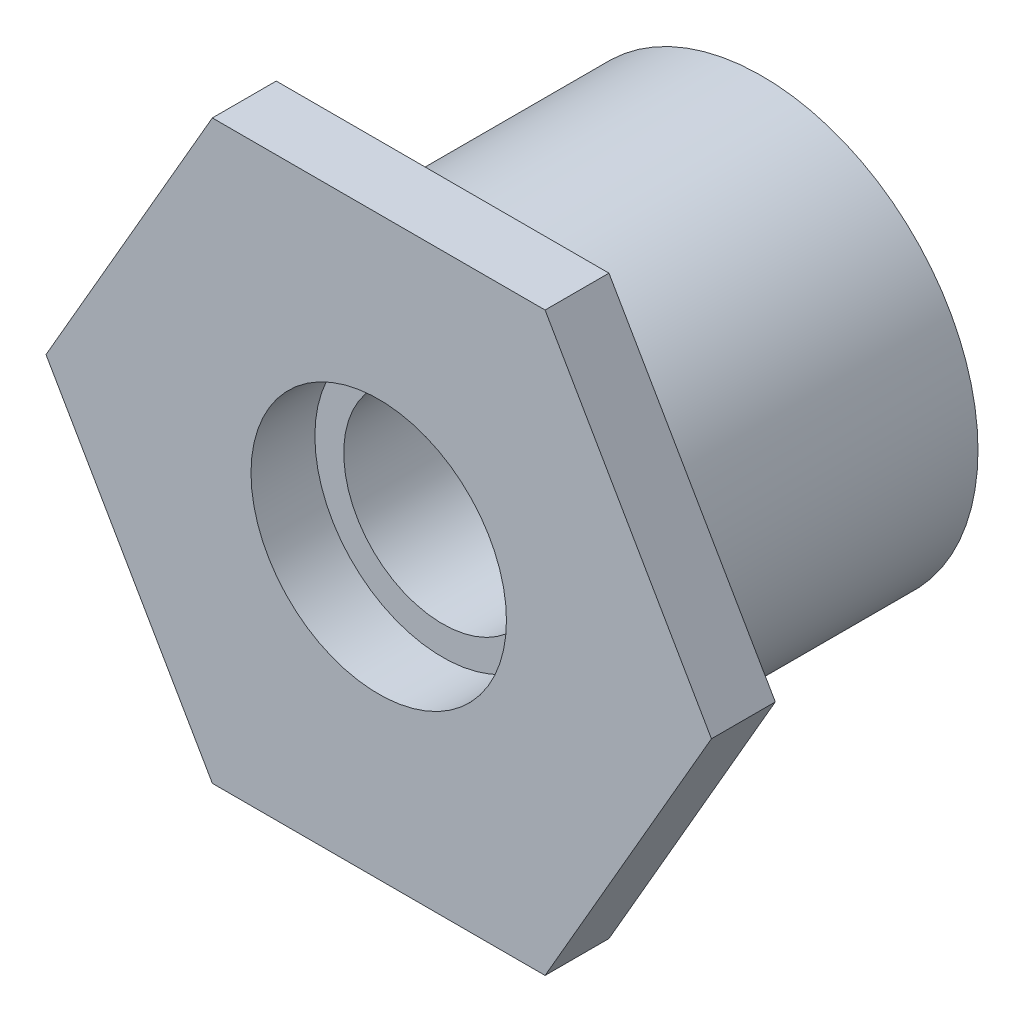
SolidWorks part; units mm, degrees
ref_plane "Front Plane" through (0, 0, 0) normal (0, 0, 1) x (1, 0, 0)
ref_plane "Top Plane" through (0, 0, 0) normal (0, 1, 0) x (1, 0, 0)
ref_plane "Right Plane" through (0, 0, 0) normal (1, 0, 0) x (0, 0, -1)
sketch "Sketch1" plane through (0, 0, 0) normal (0, 0, 1) x (1, 0, 0)
  line L1 (33.0836, 0) -> (16.5418, 28.6512)
  line L2 (16.5418, 28.6512) -> (-16.5418, 28.6512)
  line L3 (-16.5418, 28.6512) -> (-33.0836, 0)
  line L4 (-33.0836, 0) -> (-16.5418, -28.6512)
  line L5 (-16.5418, -28.6512) -> (16.5418, -28.6512)
  line L6 (16.5418, -28.6512) -> (33.0836, 0)
  circle A0 centre (0, 0) radius 12.7
  circle A1 centre (0, 0) radius 25.4
  circle A2 centre (0, 0) radius 21.4884
  circle A3 centre (0, 0) radius 9.8298
  circle A4 centre (0, 0) radius 28.6512 construction
  circle A5 centre (0, 0) radius 17.5768
  dimension "D1" = 25.4
  dimension "D2" = 50.8
  dimension "D3" = 3.9116
  dimension "D4" = 2.8702
  dimension "D6" = 3.9116
  dimension "D5" = 28.6512
extrude "Boss-Extrude1" add sketch "Sketch1" along normal blind 6.35 contours A2 A0 region at (-20.8806, 0, 0)
extrude "Boss-Extrude2" add sketch "Sketch1<3>" against normal blind 31.75 separate body contours A2 A5 region at (-20.8806, 0, 0)
sketch "Sketch1<3>" plane through (0, 0, 0) normal (0, 0, 1) x (1, 0, 0) same geometry as "Sketch1"
extrude "Boss-Extrude3" add sketch "Sketch1<4>" along normal blind 6.35 contours L5 L6 L1 L2 L3 L4 A1 | A1 A2 region at (24.0546, -13.8879, 0) region at (-24.6816, 0, 0)
sketch "Sketch1<4>" plane through (0, 0, 0) normal (0, 0, 1) x (1, 0, 0) same geometry as "Sketch1"
extrude "Boss-Extrude4" add sketch "Sketch1<5>" against normal blind 19.05 separate body contours A0 A3 region at (-12.3408, 0, 0)
sketch "Sketch1<5>" plane through (0, 0, 0) normal (0, 0, 1) x (1, 0, 0) same geometry as "Sketch1"
extrude "Boss-Extrude5" add sketch "Sketch1<6>" along direction (0, 0, 1) on the side of the normal blind 6.35 contours A5 A0 region at (-17.0797, 0, 0)
sketch "Sketch1<6>" plane through (0, 0, 0) normal (0, 0, 1) x (1, 0, 0) same geometry as "Sketch1"
